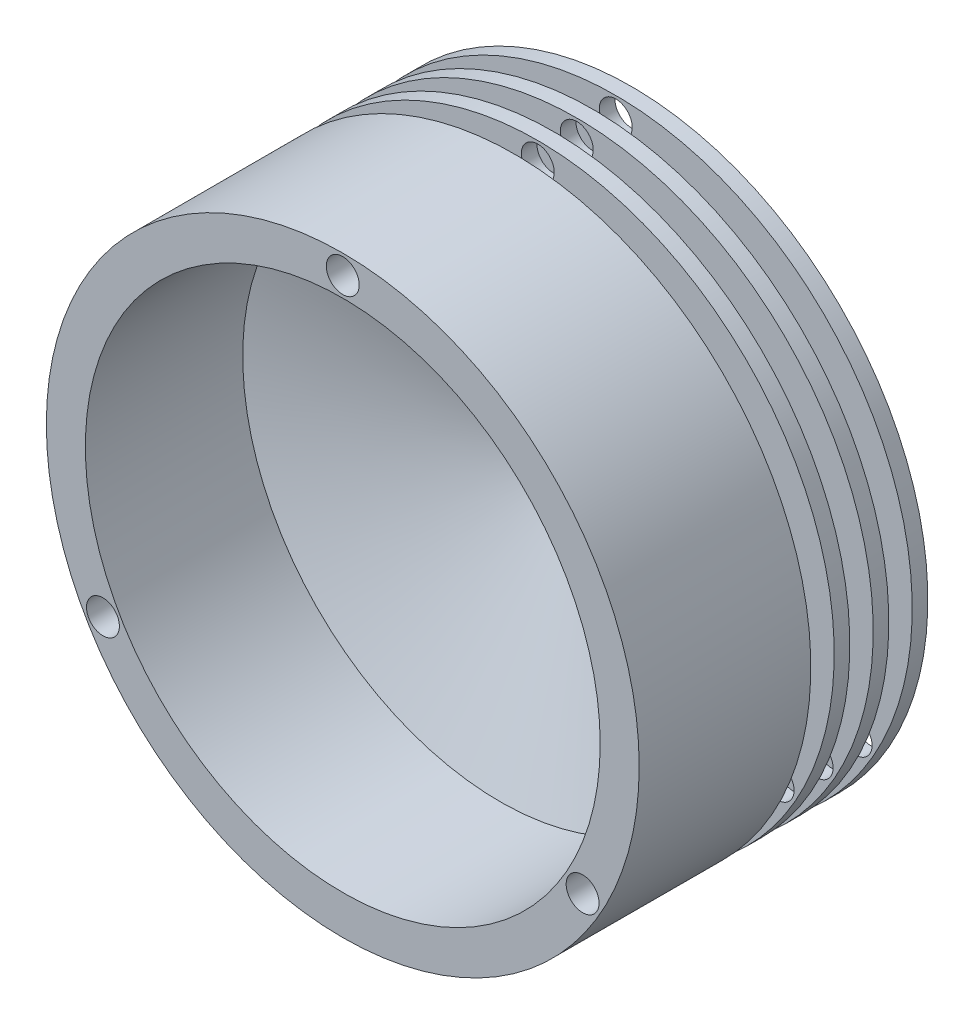
SolidWorks part; units mm, degrees
ref_plane "Plan de face" through (0, 0, 0) normal (0, 0, 1) x (1, 0, 0)
ref_plane "Plan de dessus" through (0, 0, 0) normal (0, 1, 0) x (1, 0, 0)
ref_plane "Plan de droite" through (0, 0, 0) normal (1, 0, 0) x (0, 0, -1)
sketch "Sketch1" plane through (0, 0, 0) normal (0, 0, 1) x (1, 0, 0)
  circle A0 centre (0, 0) radius 33
  circle A1 centre (0, 0) radius 38
extrude "Boss-Extrude1" add sketch "Sketch1" along normal blind 20
sketch "Sketch4" plane through (0, 0, 0) normal (0, 0, -1) x (-1, 0, 0)
  circle A0 centre (0, 0) radius 38
  circle A1 centre (0, 0) radius 6
extrude "Boss-Extrude2" add sketch "Sketch4" along normal blind 20
chamfer "Chamfer1" distance 10 angle 70 1 edges at (-6, 0, 0) first distance on face at (-6, 0, -20)
sketch "Sketch5" plane through (0, 0, -20) normal (0, 0, -1) x (-1, 0, 0)
  circle A0 centre (0, 0) radius 38
  circle A1 centre (0, 0) radius 29
extrude "Cut-Extrude1" cut sketch "Sketch5" against normal blind 3
pattern_linear "LPattern1" count 4 spacing 5 along (0, 0, 1) of "Cut-Extrude1"
sketch "Sketch6" plane through (0, 0, 20) normal (0, 0, 1) x (1, 0, 0)
  line L0 (0, 38) -> (0, 33)
  circle A0 centre (0, 0) radius 38 construction
  circle A1 centre (0, 0) radius 33 construction
hole_wizard "Hole for #4 300® SC Nuts (SP)1" positions "Sketch7" profile "Sketch9" hole size "#4-40" standard "PEM® Inch" end condition through all
sketch "Sketch7" plane through (0, 0, 20) normal (0, 0, 1) x (1, 0, 0)
  line L0 (0, 38) -> (0, 33) construction
  point P0 (0, 35.5)
sketch "Sketch9" plane through (0, 35.5, 20) normal (1, 0, 0) x (0, -1, 0)
  line L0 (0, 0) -> (0, 40)
  line L1 (0, 40) -> (2.1082, 40)
  line L2 (2.1082, 40) -> (2.1082, 0)
  line L5 (2.1082, 0) -> (0, 0)
  line L11 (0, -6.35) -> (0, 107.95) construction
  dimension "Thru Hole Dia." = 4.2164
  dimension "Thru Hole Depth" = 40
pattern_circular "CirPattern1" count 3 over 360 about axis through (0, 0, -20) along (0, 0, 1) of "Hole for #4 300® SC Nuts (SP)1"
